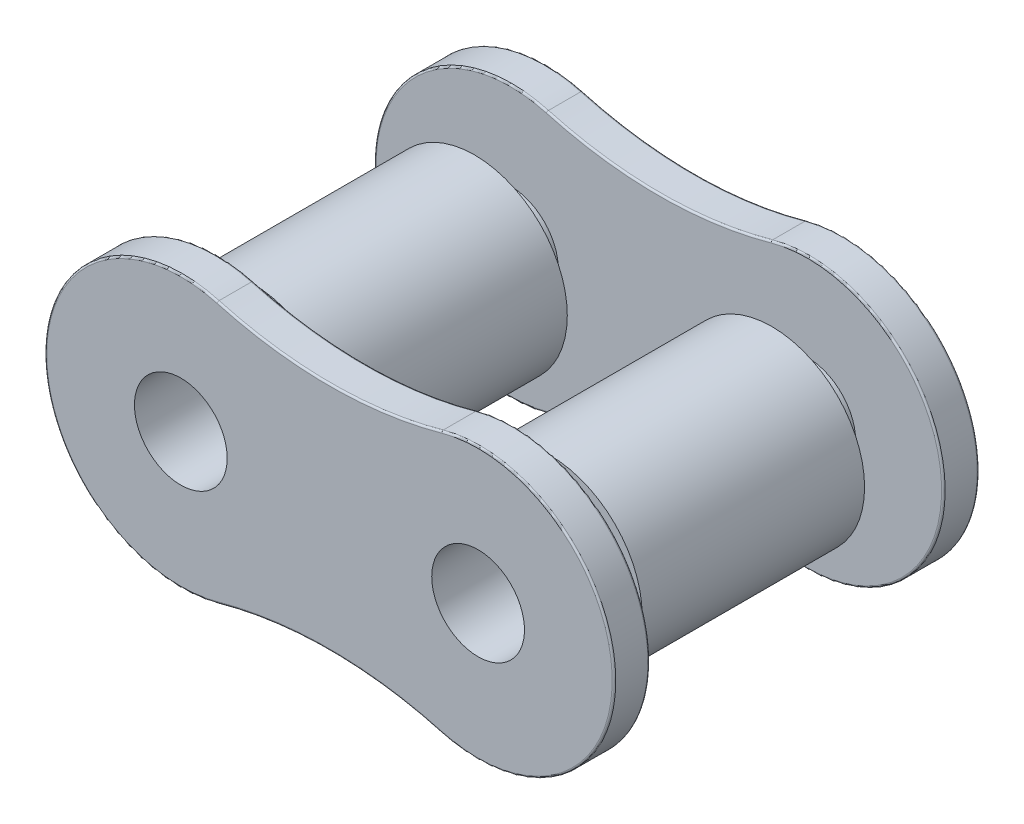
SolidWorks part; units mm, degrees
ref_plane "Front Plane" through (0, 0, 0) normal (0, 0, 1) x (1, 0, 0)
ref_plane "Top Plane" through (0, 0, 0) normal (0, 1, 0) x (1, 0, 0)
ref_plane "Right Plane" through (0, 0, 0) normal (1, 0, 0) x (0, 0, -1)
sketch "Sketch1" plane through (0, 0, 0) normal (0, 0, 1) x (1, 0, 0)
  line L0 (-6.35, 0) -> (6.35, 0) construction
  line L1 (0, -4.9333) -> (0, 4.9333) construction
  circle A0 centre (-6.35, 0) radius 1.9812
  circle A1 centre (-6.35, 0) radius 3.9624
  circle A2 centre (-6.35, 0) radius 5.8039
  circle A3 centre (6.35, 0) radius 1.9812
  circle A4 centre (6.35, 0) radius 3.9624
  circle A5 centre (6.35, 0) radius 5.8039
  point P3 (0, 0)
  point P6 (0, 0)
  dimension "D3" = 3.9624
  dimension "D4" = 7.9248
  dimension "D5" = 11.6078
  dimension "D1" = 12.7
  dimension "D2" = 9.8666
extrude "Boss-Extrude2" add sketch "Sketch1" along normal mid plane 12.548 contours A1 A0 | A4 A3 region at (-10.2003, 0, 0) region at (2.4997, 0, 0)
sketch "Sketch3" plane through (0, 0, 0) normal (0, 0, 1) x (1, 0, 0)
  line L0 (0, -4.9333) -> (0, 4.9333) construction
  line L2 (0, -4.9333) -> (0, 4.9333) construction
  circle A0 centre (-6.35, 0) radius 1.9812 construction
  circle A1 centre (6.35, 0) radius 1.9812 construction
  circle A2 centre (6.35, 0) radius 5.8039 construction
  circle A3 centre (-6.35, 0) radius 5.8039 construction
  circle A4 centre (-6.35, 0) radius 1.9812
  circle A5 centre (6.35, 0) radius 1.9812
  arc A6 (4.7879, -5.5897) -> (4.7879, 5.5897) centre (6.35, 0) ccw
  arc A7 (-4.7879, 5.5897) -> (-4.7879, -5.5897) centre (-6.35, 0) ccw
  arc A8 (4.7879, 5.5897) -> (-4.7879, 5.5897) centre (0, 22.723) cw
  arc A9 (4.7879, -5.5897) -> (-4.7879, -5.5897) centre (0, -22.723) ccw
  point P13 (0, 0)
  dimension "D1" = 9.8666
extrude "Boss-Extrude3" add sketch "Sketch3" along normal blind 1.524 from surface starting at face at (-4.3688, 0, 6.274)
extrude "Boss-Extrude4" add sketch "Sketch3<2>" against normal blind 1.524 from surface starting at face at (10.3124, 0, -6.274)
sketch "Sketch3<2>" plane through (0, 0, 0) normal (0, 0, 1) x (1, 0, 0) same geometry as "Sketch3"
fillet "Fillet1" radius 0.0762 16 edges at (0, -4.9333, -7.798) (-12.1539, 0, -7.798) (0, 4.9333, -7.798) (0, -4.9333, -6.274) (-12.1539, 0, -6.274) (0, 4.9333, -6.274) (0, -4.9333, 6.274) (-12.1539, 0, 6.274) (0, 4.9333, 6.274) (-12.1539, 0, 7.798) (0, -4.9333, 7.798) (12.1539, 0, 7.798) (12.1539, 0, -7.798) (12.1539, 0, -6.274) (12.1539, 0, 6.274) (0, 4.9333, 7.798)
ref_axis "Axis1" through (6.35, 0, 7.798) along (0, 0, -1)
ref_plane "Plane1" through (6.35, 0, 0) normal (1, 0, 0) x (0, 0, -1)
sketch "Sketch5" plane through (6.35, 0, 0) normal (1, 0, 0) x (0, 0, -1)
  line L0 (-6.274, 3.9624) -> (-6.274, 2.0574)
  line L1 (-6.274, -3.9624) -> (-6.274, 3.9624) construction
  line L2 (-6.274, 2.0574) -> (-4.75, 2.0574)
  line L3 (-4.75, 2.0574) -> (-4.75, 3.9624)
  line L4 (6.274, 3.9624) -> (-6.274, 3.9624) construction
  line L5 (-4.75, 3.9624) -> (-6.274, 3.9624)
  line L7 (-6.274, 1.9812) -> (-4.75, 1.9812) construction
  line L8 (-6.274, -5.7277) -> (-6.274, 5.7277) construction
  line L9 (-7.798, 0) -> (7.798, 0) construction
  dimension "D2" = 1.524
  dimension "D1" = 1.9812
  dimension "D3" = 0.0762
revolve "Cut-Revolve2" cut sketch "Sketch5" angle 360 about axis through (6.35, 0, 7.798) along (0, 0, -1)
mirror "Mirror2" about plane through (0, 0, 0) normal (1, 0, 0) of "Cut-Revolve2" second plane through (0, 0, 0) second plane normal (0, 0, 1)
equation "\"H\"= 0.457in"
equation "\"Roller Diameter\"= 0.312in"
equation "\"Pin Diameter\"= 0.156in"
equation "\"Pitch\"= 0.5in"
equation "\"Roller Width\"= 0.313in"
equation "\"D1@Sketch1\"=\"Pitch\""
equation "\"D2@Sketch1\"=\"H\"*0.85"
equation "\"D3@Sketch1\"=\"Pin Diameter\""
equation "\"D4@Sketch1\"=\"Roller Diameter\""
equation "\"D5@Sketch1\"=\"H\""
equation "\"D1@Sketch3\"=\"H\"*0.85"
equation "\"T\"= 0.060in"
equation "\"D1@Boss-Extrude3\"=\"T\""
equation "\"D1@Boss-Extrude4\"=\"T\""
equation "\"D1@Fillet1\"=\"T\"*0.05"
equation "\"D2@Sketch5\"=\"T\""
equation "\"D1@Sketch5\"=\"Pin Diameter\"/2"
